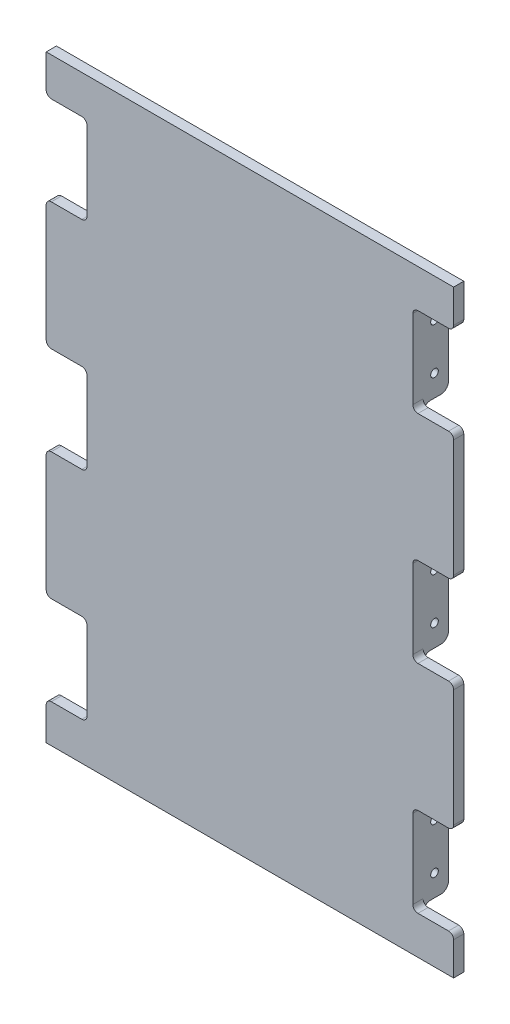
SolidWorks part; units mm, degrees
ref_plane "Front Plane" through (0, 0, 0) normal (0, 0, 1) x (1, 0, 0)
ref_plane "Top Plane" through (0, 0, 0) normal (0, 1, 0) x (1, 0, 0)
ref_plane "Right Plane" through (0, 0, 0) normal (1, 0, 0) x (0, 0, -1)
sketch "Sketch1" plane through (0, 0, 0) normal (0, 0, 1) x (1, 0, 0)
  line L0 (-64.0501, 42.5) -> (64, 42.5) construction
  line L5 (80, 25) -> (80, -25)
  line L8 (80, 25) -> (64, 25)
  line L9 (64, 60) -> (64, 25)
  line L10 (80, -60) -> (80, -75)
  line L11 (80, -60) -> (64, -60)
  line L13 (80, -25) -> (64, -25)
  line L14 (64, -60) -> (64, -25)
  line L15 (0, 75) -> (0, -75) construction
  line L25 (-64, -60) -> (-64, -25)
  line L26 (-80, -25) -> (-64, -25)
  line L27 (-80, -60) -> (-64, -60)
  line L28 (-80, -60) -> (-80, -75)
  line L29 (-64, 60) -> (-64, 25)
  line L30 (-80, 25) -> (-64, 25)
  line L32 (-80, 25) -> (-80, -25)
  line L35 (-80, -75) -> (80, -75)
  line L36 (0, 10) -> (0, 160) construction
  line L37 (-80, 160) -> (80, 160)
  line L38 (-80, 60) -> (-80, 110)
  line L39 (-80, 60) -> (-64, 60)
  line L40 (-80, 145) -> (-80, 160)
  line L41 (-80, 145) -> (-64, 145)
  line L42 (-80, 110) -> (-64, 110)
  line L43 (-64, 145) -> (-64, 110)
  line L44 (64, 145) -> (64, 110)
  line L45 (80, 110) -> (64, 110)
  line L46 (80, 145) -> (64, 145)
  line L47 (80, 145) -> (80, 160)
  line L48 (80, 60) -> (64, 60)
  line L49 (80, 60) -> (80, 110)
  point P27 (-64, 42.5)
extrude "Boss-Extrude1" add sketch "Sketch1" against normal blind 4
sketch "Sketch4" plane through (0, 0, 0) normal (0, 0, 1) x (1, 0, 0)
  line L0 (-64, -60) -> (-54, -60)
  line L5 (80, 0) -> (-80, 0) construction
  line L6 (64, 60) -> (54, 60)
  line L7 (64, 60) -> (64, 25)
  line L8 (64, 25) -> (54, 25)
  line L9 (54, 60) -> (54, 25)
  line L10 (80, -25) -> (80, 25) construction
  line L11 (-80, 25) -> (-80, -25) construction
  line L12 (54, -60) -> (54, -25)
  line L13 (64, -25) -> (54, -25)
  line L14 (64, -60) -> (64, -25)
  line L15 (64, -60) -> (54, -60)
  line L16 (0, 75) -> (0, -75) construction
  line L18 (-80, -75) -> (80, -75) construction
  line L19 (-64, -60) -> (-64, -25)
  line L20 (-64, -25) -> (-54, -25)
  line L21 (-54, -60) -> (-54, -25)
  line L22 (-54, 60) -> (-54, 25)
  line L23 (-64, 25) -> (-54, 25)
  line L24 (-64, 60) -> (-64, 25)
  line L25 (-64, 60) -> (-54, 60)
  line L26 (-80, 85) -> (80, 85) construction
  line L27 (-80, 110) -> (-80, 60) construction
  line L28 (80, 60) -> (80, 110) construction
  line L29 (-64, 110) -> (-54, 110)
  line L30 (-64, 110) -> (-64, 145)
  line L31 (-64, 145) -> (-54, 145)
  line L32 (-54, 110) -> (-54, 145)
  line L33 (54, 110) -> (54, 145)
  line L34 (64, 145) -> (54, 145)
  line L35 (64, 110) -> (64, 145)
  line L36 (64, 110) -> (54, 110)
extrude "Boss-Extrude3" add sketch "Sketch4" against normal blind 14
sketch "Sketch6" plane through (64, 0, 0) normal (1, 0, 0) x (0, 0, -1)
  line L0 (8.5, -60) -> (8.5, -25) construction
  line L1 (14, 110) -> (14, 145) construction
  line L2 (0, 60) -> (0, 110) construction
  line L3 (8.5, -42.5) -> (14, -42.5) construction
  line L4 (0, -25) -> (0, 25) construction
  line L5 (8.5, 0) -> (0, 0) construction
  line L7 (8.5, 42.5) -> (14, 42.5) construction
  line L8 (8.5, 60) -> (8.5, 25) construction
  line L9 (8.5, 85) -> (0, 85) construction
  line L11 (8.5, 110) -> (8.5, 145) construction
  line L12 (8.5, 127.5) -> (14, 127.5) construction
  line L13 (8.5, 145) -> (8.5, -60) construction
  line L16 (8.5, 42.5) -> (14, 42.5) construction
  circle A0 centre (8.5, -51.5) radius 1.5
  circle A1 centre (8.5, -33.5) radius 1.5
  circle A2 centre (8.5, 33.5) radius 1.5
  circle A3 centre (8.5, 51.5) radius 1.5
  circle A4 centre (8.5, 118.5) radius 1.5
  circle A5 centre (8.5, 136.5) radius 1.5
extrude "Cut-Extrude1" cut sketch "Sketch6" against normal up to surface (128 mm away) up to face at (-64, -42.5, -6)
fillet "Fillet2" radius 3 24 edges at (-59, -25, -14) (-59, -60, -14) (-59, 60, -14) (-59, 25, -14) (-59, 145, -14) (-59, 110, -14) (59, 145, -14) (59, 110, -14) (59, 25, -14) (59, 60, -14) (59, -25, -14) (59, -60, -14) (59, 145, -4) (59, 110, -4) (59, 60, -4) (59, 25, -4) (59, -25, -4) (59, -60, -4) (-59, -25, -4) (-59, -60, -4) (-59, 25, -4) (-59, 60, -4) (-59, 110, -4) (-59, 145, -4)
fillet "Fillet3" radius 2 24 edges at (80, -60, -2) (64, -60, -2) (80, -25, -2) (64, -25, -2) (80, 25, -2) (64, 25, -2) (64, 60, -2) (80, 60, -2) (80, 110, -2) (64, 110, -2) (64, 145, -2) (80, 145, -2) (-80, 145, -2) (-64, 145, -2) (-64, 110, -2) (-80, 110, -2) (-80, 60, -2) (-64, 60, -2) (-64, 25, -2) (-80, 25, -2) (-80, -25, -2) (-64, -25, -2) (-80, -60, -2) (-64, -60, -2)
sketch "Sketch7" plane through (0, 0, -4) normal (0, 0, -1) x (-1, 0, 0)
  line L0 (2.5, 125.5) -> (32.5, 125.5)
  line L8 (32.5, 40.5) -> (2.5, 40.5)
  line L9 (32.5, -40.5) -> (32.5, 40.5)
  line L10 (2.5, -40.5) -> (32.5, -40.5)
  line L11 (2.5, 40.5) -> (2.5, -40.5)
  line L13 (36.5, 125.5) -> (64, 125.5)
  line L16 (2.5, 44.5) -> (32.5, 44.5)
  line L17 (32.5, 44.5) -> (32.5, 125.5)
  line L19 (2.5, 125.5) -> (2.5, 44.5)
  line L24 (-32.5, -40.5) -> (-2.5, -40.5)
  line L25 (-32.5, 40.5) -> (-32.5, -40.5)
  line L26 (-2.5, 40.5) -> (-32.5, 40.5)
  line L27 (-2.5, -40.5) -> (-2.5, 40.5)
  line L32 (-2.5, 125.5) -> (-32.5, 125.5)
  line L33 (-32.5, 125.5) -> (-32.5, 44.5)
  line L34 (-32.5, 44.5) -> (-2.5, 44.5)
  line L35 (-2.5, 44.5) -> (-2.5, 125.5)
  line L76 (0, 129.5) -> (-64, 129.5)
  line L77 (-64, 129.5) -> (-64, 125.5)
  line L78 (-64, 125.5) -> (-36.5, 125.5)
  line L79 (-36.5, 125.5) -> (-36.5, 44.5)
  line L80 (-36.5, 44.5) -> (-64, 44.5)
  line L81 (-64, 44.5) -> (-64, 40.5)
  line L82 (-64, 40.5) -> (-36.5, 40.5)
  line L83 (-36.5, 40.5) -> (-36.5, -40.5)
  line L84 (-36.5, -40.5) -> (-64, -40.5)
  line L85 (-64, -40.5) -> (-64, -44.5)
  line L86 (-64, -44.5) -> (0, -44.5)
  line L87 (0, -44.5) -> (64, -44.5)
  line L88 (64, -44.5) -> (64, -40.5)
  line L89 (64, -40.5) -> (36.5, -40.5)
  line L90 (36.5, -40.5) -> (36.5, 40.5)
  line L91 (36.5, 40.5) -> (64, 40.5)
  line L92 (64, 40.5) -> (64, 44.5)
  line L93 (64, 44.5) -> (36.5, 44.5)
  line L94 (36.5, 44.5) -> (36.5, 125.5)
  line L96 (64, 125.5) -> (64, 129.5)
  line L97 (64, 129.5) -> (0, 129.5)
  dimension "D1" = 4
  dimension "D2" = 4
  dimension "D3" = 4
  dimension "D4" = 4
  dimension "D5" = 30
  dimension "D6" = 30
  dimension "D7" = 30
  dimension "D8" = 30
extrude "Boss-Extrude4" add sketch "Sketch7" along normal blind 7
fillet "Fillet4" radius 4 36 edges at (54, -44.5, -7.5) (54, -40.5, -7.5) (36.5, -40.5, -7.5) (32.5, -40.5, -7.5) (-2.5, -40.5, -7.5) (2.5, -40.5, -7.5) (-32.5, -40.5, -7.5) (-36.5, -40.5, -7.5) (-54, -44.5, -7.5) (-54, -40.5, -7.5) (-54, 40.5, -7.5) (-54, 44.5, -7.5) (-36.5, 44.5, -7.5) (-36.5, 40.5, -7.5) (-32.5, 40.5, -7.5) (-32.5, 44.5, -7.5) (54, 40.5, -7.5) (54, 44.5, -7.5) (-2.5, 44.5, -7.5) (-2.5, 40.5, -7.5) (2.5, 40.5, -7.5) (2.5, 44.5, -7.5) (36.5, 44.5, -7.5) (36.5, 40.5, -7.5) (32.5, 40.5, -7.5) (32.5, 44.5, -7.5) (54, 129.5, -7.5) (54, 125.5, -7.5) (36.5, 125.5, -7.5) (32.5, 125.5, -7.5) (2.5, 125.5, -7.5) (-2.5, 125.5, -7.5) (-32.5, 125.5, -7.5) (-36.5, 125.5, -7.5) (-54, 125.5, -7.5) (-54, 129.5, -7.5)
